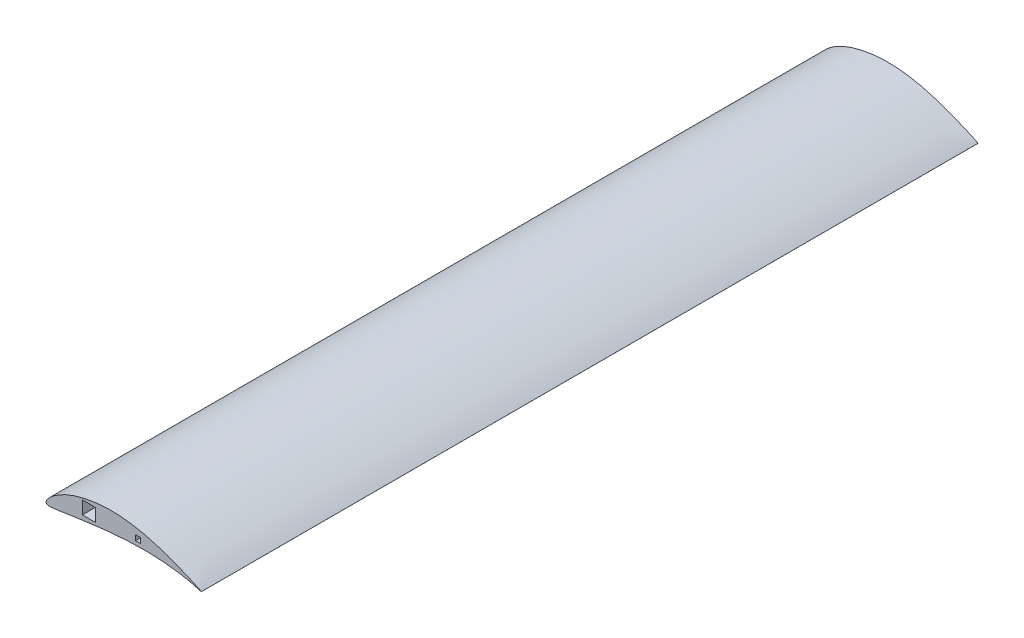
SolidWorks part; units mm, degrees
ref_plane "Front Plane" through (0, 0, 0) normal (0, 0, 1) x (1, 0, 0)
ref_plane "Top Plane" through (0, 0, 0) normal (0, 1, 0) x (1, 0, 0)
ref_plane "Right Plane" through (0, 0, 0) normal (1, 0, 0) x (0, 0, -1)
curve "Curve1"
  spline degree 3 poles (1.0002, -0.0023, 0) (1, 0, 0) (1.0002, 0.0023, 0) (0.9919, 0.0001, 0) (0.9849, 0.0027, 0) (0.9729, 0.003, 0) (0.9609, 0.0043, 0) (0.9483, 0.0054, 0) (0.9357, 0.0065, 0) (0.9231, 0.0077, 0) (0.9104, 0.0088, 0) (0.8978, 0.01, 0) (0.8852, 0.0111, 0) (0.8725, 0.0123, 0) (0.8599, 0.0134, 0) (0.8473, 0.0146, 0) (0.8347, 0.0157, 0) (0.8221, 0.0168, 0) (0.8094, 0.0179, 0) (0.7968, 0.019, 0) (0.7842, 0.0201, 0) (0.7716, 0.0211, 0) (0.759, 0.0222, 0) (0.7464, 0.0232, 0) (0.7337, 0.0243, 0) (0.7211, 0.0253, 0) (0.7085, 0.0263, 0) (0.6959, 0.0273, 0) (0.6833, 0.0283, 0) (0.6706, 0.0293, 0) (0.658, 0.0303, 0) (0.6454, 0.0313, 0) (0.6328, 0.0322, 0) (0.6202, 0.0331, 0) (0.6076, 0.0341, 0) (0.595, 0.035, 0) (0.5823, 0.0358, 0) (0.5697, 0.0367, 0) (0.5571, 0.0375, 0) (0.5446, 0.0384, 0) (0.532, 0.0392, 0) (0.5194, 0.0399, 0) (0.5068, 0.0407, 0) (0.4942, 0.0414, 0) (0.4816, 0.0421, 0) (0.469, 0.0427, 0) (0.4565, 0.0434, 0) (0.4439, 0.044, 0) (0.4313, 0.0445, 0) (0.4188, 0.0451, 0) (0.4062, 0.0456, 0) (0.3936, 0.046, 0) (0.3811, 0.0464, 0) (0.3685, 0.0468, 0) (0.356, 0.0472, 0) (0.3435, 0.0475, 0) (0.3309, 0.0477, 0) (0.3184, 0.0479, 0) (0.3059, 0.0481, 0) (0.2934, 0.0482, 0) (0.2809, 0.0482, 0) (0.2685, 0.0482, 0) (0.256, 0.0481, 0) (0.2436, 0.0479, 0) (0.2312, 0.0477, 0) (0.2189, 0.0474, 0) (0.2065, 0.047, 0) (0.1942, 0.0465, 0) (0.182, 0.0459, 0) (0.1698, 0.0452, 0) (0.1576, 0.0444, 0) (0.1456, 0.0434, 0) (0.1336, 0.0423, 0) (0.1217, 0.0411, 0) (0.1099, 0.0397, 0) (0.0983, 0.038, 0) (0.0868, 0.0362, 0) (0.0756, 0.0342, 0) (0.0647, 0.0319, 0) (0.0541, 0.0294, 0) (0.0441, 0.0266, 0) (0.0348, 0.0236, 0) (0.0266, 0.0205, 0) (0.0197, 0.0175, 0) (0.0142, 0.0146, 0) (0.0101, 0.012, 0) (0.007, 0.0098, 0) (0.0047, 0.0078, 0) (0.003, 0.006, 0) (0.0018, 0.0045, 0) (0.0009, 0.003, 0) (0.0003, 0.0017, 0) (0, 0.0004, 0) (0, -0.0008, 0) (0.0005, -0.0021, 0) (0.0015, -0.0032, 0) (0.0028, -0.0043, 0) (0.0046, -0.0054, 0) (0.0068, -0.0066, 0) (0.0097, -0.0078, 0) (0.0135, -0.0091, 0) (0.0186, -0.0106, 0) (0.0252, -0.0121, 0) (0.0334, -0.0135, 0) (0.043, -0.0148, 0) (0.0536, -0.0159, 0) (0.0648, -0.0167, 0) (0.0764, -0.0173, 0) (0.0882, -0.0177, 0) (0.1003, -0.018, 0) (0.1125, -0.0182, 0) (0.1247, -0.0183, 0) (0.1371, -0.0183, 0) (0.1495, -0.0182, 0) (0.162, -0.0181, 0) (0.1745, -0.0179, 0) (0.187, -0.0176, 0) (0.1996, -0.0174, 0) (0.2122, -0.0171, 0) (0.2248, -0.0167, 0) (0.2375, -0.0164, 0) (0.2501, -0.016, 0) (0.2628, -0.0156, 0) (0.2755, -0.0152, 0) (0.2882, -0.0147, 0) (0.3009, -0.0143, 0) (0.3136, -0.0139, 0) (0.3263, -0.0134, 0) (0.339, -0.0129, 0) (0.3517, -0.0125, 0) (0.3644, -0.012, 0) (0.3771, -0.0116, 0) (0.3897, -0.0111, 0) (0.4024, -0.0106, 0) (0.4151, -0.0102, 0) (0.4277, -0.0098, 0) (0.4404, -0.0093, 0) (0.4531, -0.0089, 0) (0.4657, -0.0085, 0) (0.4784, -0.0081, 0) (0.4911, -0.0077, 0) (0.5037, -0.0073, 0) (0.5164, -0.0069, 0) (0.5291, -0.0066, 0) (0.5417, -0.0062, 0) (0.5544, -0.0059, 0) (0.5671, -0.0055, 0) (0.5798, -0.0052, 0) (0.5924, -0.0049, 0) (0.6051, -0.0046, 0) (0.6178, -0.0044, 0) (0.6304, -0.0041, 0) (0.6431, -0.0039, 0) (0.6558, -0.0036, 0) (0.6685, -0.0034, 0) (0.6811, -0.0032, 0) (0.6938, -0.003, 0) (0.7065, -0.0029, 0) (0.7192, -0.0027, 0) (0.7318, -0.0026, 0) (0.7445, -0.0024, 0) (0.7572, -0.0023, 0) (0.7699, -0.0022, 0) (0.7826, -0.0021, 0) (0.7953, -0.002, 0) (0.8079, -0.0019, 0) (0.8206, -0.0019, 0) (0.8333, -0.0018, 0) (0.846, -0.0017, 0) (0.8588, -0.0017, 0) (0.8715, -0.0016, 0) (0.8842, -0.0015, 0) (0.8969, -0.0015, 0) (0.9096, -0.0014, 0) (0.9223, -0.0013, 0) (0.935, -0.0012, 0) (0.9477, -0.0011, 0) (0.9604, -0.0011, 0) (0.9725, -0.0007, 0) (0.9848, -0.0014, 0) (0.9918, 0.0007, 0) (1.0002, -0.0023, 0) (1, 0, 0) (1.0002, 0.0023, 0) knots -0.007874 -0.002894 -0.000332 0 0.000332 0.002885 0.007815 0.013623 0.01978 0.026037 0.032316 0.038604 0.044895 0.051184 0.057469 0.06375 0.070028 0.076304 0.082578 0.088851 0.095124 0.101396 0.107668 0.113941 0.120213 0.126487 0.132762 0.139036 0.145311 0.151585 0.157859 0.16413 0.170401 0.17667 0.182937 0.189202 0.195466 0.201728 0.207987 0.214245 0.2205 0.226754 0.233005 0.239253 0.2455 0.251744 0.257986 0.264226 0.270464 0.2767 0.282933 0.289165 0.295394 0.30162 0.307843 0.314063 0.32028 0.326491 0.332699 0.3389 0.345096 0.351285 0.357467 0.363641 0.369805 0.375959 0.382101 0.38823 0.394345 0.400443 0.406521 0.412577 0.418607 0.424607 0.430573 0.436498 0.442374 0.448192 0.453938 0.459595 0.465142 0.470542 0.475738 0.480625 0.48504 0.488808 0.491844 0.494208 0.496047 0.497501 0.498679 0.499657 0.500486 0.501199 0.501823 0.502412 0.503041 0.50376 0.504602 0.505602 0.50682 0.508337 0.510284 0.512841 0.516185 0.520365 0.525232 0.530552 0.536146 0.541914 0.547804 0.553781 0.559821 0.565909 0.57203 0.578179 0.584352 0.590546 0.596759 0.60299 0.609237 0.615497 0.621768 0.62805 0.634339 0.640634 0.646932 0.653231 0.659529 0.665824 0.672115 0.678404 0.684692 0.690977 0.69726 0.703542 0.709822 0.716099 0.722375 0.728651 0.734927 0.741206 0.747487 0.753768 0.76005 0.766331 0.772611 0.778892 0.785172 0.791451 0.79773 0.804009 0.810289 0.816569 0.822848 0.829126 0.835406 0.841685 0.847965 0.854245 0.860527 0.866808 0.87309 0.879373 0.885657 0.891942 0.898228 0.904515 0.910804 0.917095 0.923389 0.929686 0.935986 0.942288 0.948588 0.954885 0.961183 0.96748 0.973774 0.980051 0.986247 0.992126 0.997106 0.999668 1 1.000332 1.002885 1.007815 periodic
curve "Curve6"
  spline degree 3 poles (0, 0, 0) (0.0002, 0.0017, 0) (0.0007, 0.0052, 0) (0.0046, 0.01, 0) (0.01, 0.0151, 0) (0.0174, 0.0207, 0) (0.027, 0.0264, 0) (0.0385, 0.0321, 0) (0.052, 0.0379, 0) (0.0675, 0.0434, 0) (0.0847, 0.0488, 0) (0.1038, 0.0538, 0) (0.1245, 0.0586, 0) (0.1469, 0.063, 0) (0.1707, 0.0671, 0) (0.196, 0.0706, 0) (0.2226, 0.0737, 0) (0.2503, 0.0762, 0) (0.2792, 0.0783, 0) (0.3089, 0.0796, 0) (0.3395, 0.0805, 0) (0.3708, 0.0807, 0) (0.4026, 0.0805, 0) (0.4348, 0.0796, 0) (0.4674, 0.0782, 0) (0.5, 0.0763, 0) (0.5327, 0.074, 0) (0.5652, 0.0714, 0) (0.5974, 0.0683, 0) (0.6292, 0.0649, 0) (0.6605, 0.0611, 0) (0.6911, 0.057, 0) (0.7209, 0.0527, 0) (0.7497, 0.0482, 0) (0.7774, 0.0435, 0) (0.804, 0.0388, 0) (0.8292, 0.0342, 0) (0.8531, 0.0298, 0) (0.8754, 0.0255, 0) (0.8961, 0.0215, 0) (0.9151, 0.0177, 0) (0.9324, 0.0142, 0) (0.9478, 0.0111, 0) (0.9613, 0.0083, 0) (0.9728, 0.0059, 0) (0.9823, 0.0039, 0) (0.9897, 0.0023, 0) (0.9949, 0.0006, 0) (0.9983, 0.0007, 0) (0.9996, 0.0001, 0) (1, 0, 0) knots 0 0 0 0 0.004816 0.010311 0.017533 0.026619 0.037456 0.050036 0.064348 0.080358 0.098009 0.117234 0.138018 0.160262 0.183891 0.2088 0.234911 0.262128 0.290345 0.319442 0.34932 0.379858 0.410934 0.442439 0.474224 0.506171 0.538142 0.570006 0.601639 0.632894 0.663653 0.693783 0.723155 0.751647 0.779129 0.805464 0.830536 0.854232 0.876442 0.897072 0.916014 0.933209 0.948567 0.962012 0.9735 0.982962 0.990398 0.99574 0.998893 1 1 1 1
curve "Curve7"
  spline degree 3 poles (0.0009, -0.0041, 0) (-0.0004, 0.0004, 0) (0.0009, 0.0052, 0) (0.0045, 0.01, 0) (0.01, 0.0151, 0) (0.0174, 0.0207, 0) (0.027, 0.0264, 0) (0.0385, 0.0321, 0) (0.052, 0.0379, 0) (0.0675, 0.0434, 0) (0.0847, 0.0488, 0) (0.1038, 0.0538, 0) (0.1245, 0.0586, 0) (0.1469, 0.063, 0) (0.1707, 0.0671, 0) (0.196, 0.0706, 0) (0.2226, 0.0737, 0) (0.2503, 0.0762, 0) (0.2792, 0.0783, 0) (0.3089, 0.0796, 0) (0.3395, 0.0805, 0) (0.3708, 0.0807, 0) (0.4026, 0.0805, 0) (0.4348, 0.0796, 0) (0.4674, 0.0782, 0) (0.5, 0.0763, 0) (0.5327, 0.074, 0) (0.5652, 0.0714, 0) (0.5974, 0.0683, 0) (0.6292, 0.0649, 0) (0.6605, 0.0611, 0) (0.6911, 0.057, 0) (0.7209, 0.0527, 0) (0.7497, 0.0482, 0) (0.7774, 0.0435, 0) (0.804, 0.0388, 0) (0.8292, 0.0342, 0) (0.8531, 0.0298, 0) (0.8754, 0.0255, 0) (0.8961, 0.0215, 0) (0.9151, 0.0177, 0) (0.9324, 0.0142, 0) (0.9478, 0.0111, 0) (0.9613, 0.0083, 0) (0.9728, 0.0059, 0) (0.9823, 0.0038, 0) (0.9896, 0.0024, 0) (0.9953, 0.0005, 0) (0.9978, 0.0008, 0) (1.0006, -0.0001, 0) (0.9977, 0.0003, 0) (0.9953, 0, 0) (0.9896, 0.0009, 0) (0.9823, 0.0014, 0) (0.9728, 0.0025, 0) (0.9613, 0.0036, 0) (0.9478, 0.0048, 0) (0.9324, 0.006, 0) (0.9151, 0.0072, 0) (0.8961, 0.0083, 0) (0.8754, 0.0093, 0) (0.8531, 0.0102, 0) (0.8292, 0.0108, 0) (0.8039, 0.0112, 0) (0.7774, 0.0112, 0) (0.7496, 0.0109, 0) (0.7208, 0.0102, 0) (0.6911, 0.0092, 0) (0.6605, 0.0079, 0) (0.6292, 0.0062, 0) (0.5974, 0.004, 0) (0.5652, 0.0016, 0) (0.5326, -0.0011, 0) (0.5, -0.0039, 0) (0.4673, -0.0069, 0) (0.4348, -0.0098, 0) (0.4026, -0.0128, 0) (0.3708, -0.0154, 0) (0.3395, -0.018, 0) (0.3089, -0.0201, 0) (0.2792, -0.022, 0) (0.2504, -0.0233, 0) (0.2226, -0.0244, 0) (0.1961, -0.0249, 0) (0.1708, -0.0253, 0) (0.147, -0.0252, 0) (0.1246, -0.0248, 0) (0.1039, -0.024, 0) (0.0848, -0.023, 0) (0.0676, -0.0217, 0) (0.0522, -0.0201, 0) (0.0387, -0.0182, 0) (0.0271, -0.0161, 0) (0.0176, -0.0135, 0) (0.01, -0.0109, 0) (0.0046, -0.0077, 0) (0.0009, -0.0041, 0) (-0.0004, 0.0004, 0) (0.0009, 0.0052, 0) knots -0.007287 -0.004212 -0.00188 0 0.002428 0.005198 0.00884 0.013421 0.018885 0.025227 0.032443 0.040515 0.049414 0.059107 0.069586 0.080801 0.092714 0.105273 0.118437 0.13216 0.146386 0.161056 0.17612 0.191517 0.207184 0.223068 0.239094 0.255201 0.27132 0.287385 0.303334 0.319092 0.3346 0.349791 0.364599 0.378965 0.392821 0.406098 0.418739 0.430686 0.441884 0.452285 0.461835 0.470504 0.478247 0.485026 0.490819 0.495589 0.499338 0.502031 0.503621 0.504179 0.504707 0.506286 0.508919 0.512589 0.517281 0.522978 0.529643 0.537254 0.545772 0.555157 0.565377 0.576386 0.588132 0.60057 0.613645 0.627312 0.641507 0.656169 0.671241 0.686661 0.702362 0.718285 0.734352 0.750492 0.766637 0.782713 0.798656 0.81438 0.829825 0.844919 0.8596 0.873808 0.887483 0.900562 0.912999 0.924742 0.935744 0.94596 0.955342 0.963865 0.971494 0.978201 0.983972 0.988807 0.992713 0.995788 0.99812 1 1.002428 1.005198 1.00884 periodic
curve "Curve8"
  spline degree 3 poles (1, 0.0001, 0) (0.9992, 0.0006, 0) (0.9962, 0.0026, 0) (0.9897, 0.0065, 0) (0.9795, 0.0117, 0) (0.966, 0.0177, 0) (0.9494, 0.025, 0) (0.9297, 0.0336, 0) (0.9068, 0.0433, 0) (0.8812, 0.0541, 0) (0.853, 0.0656, 0) (0.8225, 0.0776, 0) (0.79, 0.0897, 0) (0.7558, 0.1017, 0) (0.7202, 0.1132, 0) (0.6835, 0.1241, 0) (0.6459, 0.134, 0) (0.6078, 0.1427, 0) (0.5695, 0.1499, 0) (0.5311, 0.1556, 0) (0.4927, 0.1597, 0) (0.4545, 0.162, 0) (0.4165, 0.1627, 0) (0.3791, 0.1616, 0) (0.3423, 0.1589, 0) (0.3063, 0.1546, 0) (0.2715, 0.1489, 0) (0.2379, 0.1418, 0) (0.2058, 0.1335, 0) (0.1754, 0.124, 0) (0.1469, 0.1134, 0) (0.1204, 0.1018, 0) (0.0962, 0.0895, 0) (0.0744, 0.0767, 0) (0.0552, 0.0638, 0) (0.0386, 0.051, 0) (0.0247, 0.0387, 0) (0.0137, 0.027, 0) (0.0057, 0.0163, 0) (0.0011, 0.0075, 0) (-0.0003, 0.0005, 0) (0.0007, -0.0053, 0) (0.0058, -0.01, 0) (0.0142, -0.0123, 0) (0.0253, -0.0129, 0) (0.0391, -0.0122, 0) (0.0556, -0.0102, 0) (0.0748, -0.0075, 0) (0.0966, -0.0042, 0) (0.1207, -0.0007, 0) (0.1472, 0.0033, 0) (0.1757, 0.0076, 0) (0.206, 0.0121, 0) (0.2381, 0.0168, 0) (0.2716, 0.0215, 0) (0.3064, 0.0261, 0) (0.3423, 0.0305, 0) (0.3791, 0.0347, 0) (0.4165, 0.0385, 0) (0.4544, 0.0419, 0) (0.4926, 0.0448, 0) (0.531, 0.047, 0) (0.5694, 0.0486, 0) (0.6077, 0.0495, 0) (0.6458, 0.0495, 0) (0.6833, 0.0486, 0) (0.7201, 0.0469, 0) (0.7557, 0.0444, 0) (0.7899, 0.0412, 0) (0.8225, 0.0376, 0) (0.853, 0.0334, 0) (0.8812, 0.0289, 0) (0.9069, 0.0241, 0) (0.9297, 0.0193, 0) (0.9494, 0.0145, 0) (0.966, 0.0098, 0) (0.9793, 0.0054, 0) (0.9895, 0.0024, 0) (0.9961, 0.0007, 0) (0.9992, 0.0001, 0) (1, -0.0001, 0) knots 0 0 0 0 0.001413 0.005226 0.010781 0.017816 0.026461 0.036791 0.048686 0.062017 0.076639 0.092363 0.109003 0.126387 0.144339 0.162701 0.181313 0.200023 0.218713 0.237261 0.255692 0.274037 0.292193 0.310133 0.327788 0.345097 0.362002 0.378421 0.394287 0.409543 0.424114 0.437938 0.450942 0.463044 0.474154 0.484165 0.493024 0.500713 0.507126 0.51213 0.514904 0.517171 0.520262 0.524245 0.529498 0.536092 0.544061 0.553363 0.563905 0.575615 0.58842 0.602227 0.616944 0.632457 0.648676 0.665501 0.682818 0.700538 0.718564 0.736789 0.755151 0.773513 0.791878 0.810245 0.828489 0.846493 0.864125 0.881249 0.897725 0.913415 0.928184 0.941897 0.954411 0.965603 0.97535 0.983576 0.990285 0.995433 0.9988 1 1 1 1
sketch "Sketch3" plane through (0, 0, 0) normal (0, 0, 1) x (1, 0, 0)
  line L0 (0, 0) -> (50, 0) construction
  line L1 (0.2298, 0.0405) -> (0.2298, 0.0158) construction
  line L2 (0.1804, 0.0405) -> (0.2298, 0.0405)
  line L3 (0.1804, 0.0405) -> (0.1804, -0.0089)
  line L4 (0.1804, -0.0089) -> (0.2298, -0.0089)
  line L5 (0.2298, 0.0405) -> (0.2298, -0.0089)
  line L6 (0.4642, 0.0242) -> (0.4889, 0.0242)
  line L7 (0.4642, 0.0242) -> (0.4642, -0.0005)
  line L8 (0.4642, -0.0005) -> (0.4889, -0.0005)
  line L9 (0.4889, 0.0242) -> (0.4889, -0.0005)
  line L10 (0.2298, 0.0158) -> (0.2146, 0.0158) construction
  line L11 (0.2146, 0.0158) -> (0.2146, 0.0405) construction
  line L12 (0.2146, 0.0405) -> (0.2298, 0.0405) construction
  line L13 (0, 0) -> (500, 0) construction
  line L14 (0.1804, 0.0458) -> (0.1804, -0.0178) construction
  line L15 (0, 0) -> (0, -165.9812) construction
  line L16 (0, -165.9812) -> (300, -165.9812) construction
  line L17 (72.7802, 36.2202) -> (92.7802, 36.2202) construction
  line L18 (70.2802, 13.7202) -> (95.2802, 13.7202)
  line L19 (70.2802, 13.7202) -> (70.2802, 38.7202)
  line L20 (70.2802, 38.7202) -> (95.2802, 38.7202)
  line L21 (95.2802, 13.7202) -> (95.2802, 38.7202)
  line L22 (92.7802, 16.2202) -> (92.7802, 36.2202) construction
  line L23 (72.7802, 16.2202) -> (92.7802, 16.2202) construction
  line L24 (72.7802, 16.2202) -> (72.7802, 36.2202) construction
  line L25 (300, -0.018) -> (300, 0.015)
  line L26 (172.9506, 31.8748) -> (182.9506, 31.8748)
  line L27 (172.9506, 31.8748) -> (172.9506, 21.8748)
  line L28 (172.9506, 21.8748) -> (182.9506, 21.8748)
  line L29 (182.9506, 31.8748) -> (182.9506, 21.8748)
  spline S0 degree 3 poles (1.0002, -0.0023) (1, 0) (1.0002, 0.0023) (0.9919, 0.0001) (0.9849, 0.0027) (0.9729, 0.003) (0.9609, 0.0043) (0.9483, 0.0054) (0.9357, 0.0065) (0.9231, 0.0077) (0.9104, 0.0088) (0.8978, 0.01) (0.8852, 0.0111) (0.8725, 0.0123) (0.8599, 0.0134) (0.8473, 0.0146) (0.8347, 0.0157) (0.8221, 0.0168) (0.8094, 0.0179) (0.7968, 0.019) (0.7842, 0.0201) (0.7716, 0.0211) (0.759, 0.0222) (0.7464, 0.0232) (0.7337, 0.0243) (0.7211, 0.0253) (0.7085, 0.0263) (0.6959, 0.0273) (0.6833, 0.0283) (0.6706, 0.0293) (0.658, 0.0303) (0.6454, 0.0313) (0.6328, 0.0322) (0.6202, 0.0331) (0.6076, 0.0341) (0.595, 0.035) (0.5823, 0.0358) (0.5697, 0.0367) (0.5571, 0.0375) (0.5446, 0.0384) (0.532, 0.0392) (0.5194, 0.0399) (0.5068, 0.0407) (0.4942, 0.0414) (0.4816, 0.0421) (0.469, 0.0427) (0.4565, 0.0434) (0.4439, 0.044) (0.4313, 0.0445) (0.4188, 0.0451) (0.4062, 0.0456) (0.3936, 0.046) (0.3811, 0.0464) (0.3685, 0.0468) (0.356, 0.0472) (0.3435, 0.0475) (0.3309, 0.0477) (0.3184, 0.0479) (0.3059, 0.0481) (0.2934, 0.0482) (0.2809, 0.0482) (0.2685, 0.0482) (0.256, 0.0481) (0.2436, 0.0479) (0.2312, 0.0477) (0.2189, 0.0474) (0.2065, 0.047) (0.1942, 0.0465) (0.182, 0.0459) (0.1698, 0.0452) (0.1576, 0.0444) (0.1456, 0.0434) (0.1336, 0.0423) (0.1217, 0.0411) (0.1099, 0.0397) (0.0983, 0.038) (0.0868, 0.0362) (0.0756, 0.0342) (0.0647, 0.0319) (0.0541, 0.0294) (0.0441, 0.0266) (0.0348, 0.0236) (0.0266, 0.0205) (0.0197, 0.0175) (0.0142, 0.0146) (0.0101, 0.012) (0.007, 0.0098) (0.0047, 0.0078) (0.003, 0.006) (0.0018, 0.0045) (0.0009, 0.003) (0.0003, 0.0017) (0, 0.0004) (0, -0.0008) (0.0005, -0.0021) (0.0015, -0.0032) (0.0028, -0.0043) (0.0046, -0.0054) (0.0068, -0.0066) (0.0097, -0.0078) (0.0135, -0.0091) (0.0186, -0.0106) (0.0252, -0.0121) (0.0334, -0.0135) (0.043, -0.0148) (0.0536, -0.0159) (0.0648, -0.0167) (0.0764, -0.0173) (0.0882, -0.0177) (0.1003, -0.018) (0.1125, -0.0182) (0.1247, -0.0183) (0.1371, -0.0183) (0.1495, -0.0182) (0.162, -0.0181) (0.1745, -0.0179) (0.187, -0.0176) (0.1996, -0.0174) (0.2122, -0.0171) (0.2248, -0.0167) (0.2375, -0.0164) (0.2501, -0.016) (0.2628, -0.0156) (0.2755, -0.0152) (0.2882, -0.0147) (0.3009, -0.0143) (0.3136, -0.0139) (0.3263, -0.0134) (0.339, -0.0129) (0.3517, -0.0125) (0.3644, -0.012) (0.3771, -0.0116) (0.3897, -0.0111) (0.4024, -0.0106) (0.4151, -0.0102) (0.4277, -0.0098) (0.4404, -0.0093) (0.4531, -0.0089) (0.4657, -0.0085) (0.4784, -0.0081) (0.4911, -0.0077) (0.5037, -0.0073) (0.5164, -0.0069) (0.5291, -0.0066) (0.5417, -0.0062) (0.5544, -0.0059) (0.5671, -0.0055) (0.5798, -0.0052) (0.5924, -0.0049) (0.6051, -0.0046) (0.6178, -0.0044) (0.6304, -0.0041) (0.6431, -0.0039) (0.6558, -0.0036) (0.6685, -0.0034) (0.6811, -0.0032) (0.6938, -0.003) (0.7065, -0.0029) (0.7192, -0.0027) (0.7318, -0.0026) (0.7445, -0.0024) (0.7572, -0.0023) (0.7699, -0.0022) (0.7826, -0.0021) (0.7953, -0.002) (0.8079, -0.0019) (0.8206, -0.0019) (0.8333, -0.0018) (0.846, -0.0017) (0.8588, -0.0017) (0.8715, -0.0016) (0.8842, -0.0015) (0.8969, -0.0015) (0.9096, -0.0014) (0.9223, -0.0013) (0.935, -0.0012) (0.9477, -0.0011) (0.9604, -0.0011) (0.9725, -0.0007) (0.9848, -0.0014) (0.9918, 0.0007) (1.0002, -0.0023) (1, 0) (1.0002, 0.0023) knots -0.007874 -0.002894 -0.000332 0 0.000332 0.002885 0.007815 0.013623 0.01978 0.026037 0.032316 0.038604 0.044895 0.051184 0.057469 0.06375 0.070028 0.076304 0.082578 0.088851 0.095124 0.101396 0.107668 0.113941 0.120213 0.126487 0.132762 0.139036 0.145311 0.151585 0.157859 0.16413 0.170401 0.17667 0.182937 0.189202 0.195466 0.201728 0.207987 0.214245 0.2205 0.226754 0.233005 0.239253 0.2455 0.251744 0.257986 0.264226 0.270464 0.2767 0.282933 0.289165 0.295394 0.30162 0.307843 0.314063 0.32028 0.326491 0.332699 0.3389 0.345096 0.351285 0.357467 0.363641 0.369805 0.375959 0.382101 0.38823 0.394345 0.400443 0.406521 0.412577 0.418607 0.424607 0.430573 0.436498 0.442374 0.448192 0.453938 0.459595 0.465142 0.470542 0.475738 0.480625 0.48504 0.488808 0.491844 0.494208 0.496047 0.497501 0.498679 0.499657 0.500486 0.501199 0.501823 0.502412 0.503041 0.50376 0.504602 0.505602 0.50682 0.508337 0.510284 0.512841 0.516185 0.520365 0.525232 0.530552 0.536146 0.541914 0.547804 0.553781 0.559821 0.565909 0.57203 0.578179 0.584352 0.590546 0.596759 0.60299 0.609237 0.615497 0.621768 0.62805 0.634339 0.640634 0.646932 0.653231 0.659529 0.665824 0.672115 0.678404 0.684692 0.690977 0.69726 0.703542 0.709822 0.716099 0.722375 0.728651 0.734927 0.741206 0.747487 0.753768 0.76005 0.766331 0.772611 0.778892 0.785172 0.791451 0.79773 0.804009 0.810289 0.816569 0.822848 0.829126 0.835406 0.841685 0.847965 0.854245 0.860527 0.866808 0.87309 0.879373 0.885657 0.891942 0.898228 0.904515 0.910804 0.917095 0.923389 0.929686 0.935986 0.942288 0.948588 0.954885 0.961183 0.96748 0.973774 0.980051 0.986247 0.992126 0.997106 0.999668 1 1.000332 1.002885 1.007815 only from (1, 0) to (1, 0) construction
  spline S1 degree 3 poles (1.0002, -0.0023) (1, 0) (1.0002, 0.0023) (0.9919, 0.0001) (0.9849, 0.0027) (0.9729, 0.003) (0.9609, 0.0043) (0.9483, 0.0054) (0.9357, 0.0065) (0.9231, 0.0077) (0.9104, 0.0088) (0.8978, 0.01) (0.8852, 0.0111) (0.8725, 0.0123) (0.8599, 0.0134) (0.8473, 0.0146) (0.8347, 0.0157) (0.8221, 0.0168) (0.8094, 0.0179) (0.7968, 0.019) (0.7842, 0.0201) (0.7716, 0.0211) (0.759, 0.0222) (0.7464, 0.0232) (0.7337, 0.0243) (0.7211, 0.0253) (0.7085, 0.0263) (0.6959, 0.0273) (0.6833, 0.0283) (0.6706, 0.0293) (0.658, 0.0303) (0.6454, 0.0313) (0.6328, 0.0322) (0.6202, 0.0331) (0.6076, 0.0341) (0.595, 0.035) (0.5823, 0.0358) (0.5697, 0.0367) (0.5571, 0.0375) (0.5446, 0.0384) (0.532, 0.0392) (0.5194, 0.0399) (0.5068, 0.0407) (0.4942, 0.0414) (0.4816, 0.0421) (0.469, 0.0427) (0.4565, 0.0434) (0.4439, 0.044) (0.4313, 0.0445) (0.4188, 0.0451) (0.4062, 0.0456) (0.3936, 0.046) (0.3811, 0.0464) (0.3685, 0.0468) (0.356, 0.0472) (0.3435, 0.0475) (0.3309, 0.0477) (0.3184, 0.0479) (0.3059, 0.0481) (0.2934, 0.0482) (0.2809, 0.0482) (0.2685, 0.0482) (0.256, 0.0481) (0.2436, 0.0479) (0.2312, 0.0477) (0.2189, 0.0474) (0.2065, 0.047) (0.1942, 0.0465) (0.182, 0.0459) (0.1698, 0.0452) (0.1576, 0.0444) (0.1456, 0.0434) (0.1336, 0.0423) (0.1217, 0.0411) (0.1099, 0.0397) (0.0983, 0.038) (0.0868, 0.0362) (0.0756, 0.0342) (0.0647, 0.0319) (0.0541, 0.0294) (0.0441, 0.0266) (0.0348, 0.0236) (0.0266, 0.0205) (0.0197, 0.0175) (0.0142, 0.0146) (0.0101, 0.012) (0.007, 0.0098) (0.0047, 0.0078) (0.003, 0.006) (0.0018, 0.0045) (0.0009, 0.003) (0.0003, 0.0017) (0, 0.0004) (0, -0.0008) (0.0005, -0.0021) (0.0015, -0.0032) (0.0028, -0.0043) (0.0046, -0.0054) (0.0068, -0.0066) (0.0097, -0.0078) (0.0135, -0.0091) (0.0186, -0.0106) (0.0252, -0.0121) (0.0334, -0.0135) (0.043, -0.0148) (0.0536, -0.0159) (0.0648, -0.0167) (0.0764, -0.0173) (0.0882, -0.0177) (0.1003, -0.018) (0.1125, -0.0182) (0.1247, -0.0183) (0.1371, -0.0183) (0.1495, -0.0182) (0.162, -0.0181) (0.1745, -0.0179) (0.187, -0.0176) (0.1996, -0.0174) (0.2122, -0.0171) (0.2248, -0.0167) (0.2375, -0.0164) (0.2501, -0.016) (0.2628, -0.0156) (0.2755, -0.0152) (0.2882, -0.0147) (0.3009, -0.0143) (0.3136, -0.0139) (0.3263, -0.0134) (0.339, -0.0129) (0.3517, -0.0125) (0.3644, -0.012) (0.3771, -0.0116) (0.3897, -0.0111) (0.4024, -0.0106) (0.4151, -0.0102) (0.4277, -0.0098) (0.4404, -0.0093) (0.4531, -0.0089) (0.4657, -0.0085) (0.4784, -0.0081) (0.4911, -0.0077) (0.5037, -0.0073) (0.5164, -0.0069) (0.5291, -0.0066) (0.5417, -0.0062) (0.5544, -0.0059) (0.5671, -0.0055) (0.5798, -0.0052) (0.5924, -0.0049) (0.6051, -0.0046) (0.6178, -0.0044) (0.6304, -0.0041) (0.6431, -0.0039) (0.6558, -0.0036) (0.6685, -0.0034) (0.6811, -0.0032) (0.6938, -0.003) (0.7065, -0.0029) (0.7192, -0.0027) (0.7318, -0.0026) (0.7445, -0.0024) (0.7572, -0.0023) (0.7699, -0.0022) (0.7826, -0.0021) (0.7953, -0.002) (0.8079, -0.0019) (0.8206, -0.0019) (0.8333, -0.0018) (0.846, -0.0017) (0.8588, -0.0017) (0.8715, -0.0016) (0.8842, -0.0015) (0.8969, -0.0015) (0.9096, -0.0014) (0.9223, -0.0013) (0.935, -0.0012) (0.9477, -0.0011) (0.9604, -0.0011) (0.9725, -0.0007) (0.9848, -0.0014) (0.9918, 0.0007) (1.0002, -0.0023) (1, 0) (1.0002, 0.0023) knots -0.007874 -0.002894 -0.000332 0 0.000332 0.002885 0.007815 0.013623 0.01978 0.026037 0.032316 0.038604 0.044895 0.051184 0.057469 0.06375 0.070028 0.076304 0.082578 0.088851 0.095124 0.101396 0.107668 0.113941 0.120213 0.126487 0.132762 0.139036 0.145311 0.151585 0.157859 0.16413 0.170401 0.17667 0.182937 0.189202 0.195466 0.201728 0.207987 0.214245 0.2205 0.226754 0.233005 0.239253 0.2455 0.251744 0.257986 0.264226 0.270464 0.2767 0.282933 0.289165 0.295394 0.30162 0.307843 0.314063 0.32028 0.326491 0.332699 0.3389 0.345096 0.351285 0.357467 0.363641 0.369805 0.375959 0.382101 0.38823 0.394345 0.400443 0.406521 0.412577 0.418607 0.424607 0.430573 0.436498 0.442374 0.448192 0.453938 0.459595 0.465142 0.470542 0.475738 0.480625 0.48504 0.488808 0.491844 0.494208 0.496047 0.497501 0.498679 0.499657 0.500486 0.501199 0.501823 0.502412 0.503041 0.50376 0.504602 0.505602 0.50682 0.508337 0.510284 0.512841 0.516185 0.520365 0.525232 0.530552 0.536146 0.541914 0.547804 0.553781 0.559821 0.565909 0.57203 0.578179 0.584352 0.590546 0.596759 0.60299 0.609237 0.615497 0.621768 0.62805 0.634339 0.640634 0.646932 0.653231 0.659529 0.665824 0.672115 0.678404 0.684692 0.690977 0.69726 0.703542 0.709822 0.716099 0.722375 0.728651 0.734927 0.741206 0.747487 0.753768 0.76005 0.766331 0.772611 0.778892 0.785172 0.791451 0.79773 0.804009 0.810289 0.816569 0.822848 0.829126 0.835406 0.841685 0.847965 0.854245 0.860527 0.866808 0.87309 0.879373 0.885657 0.891942 0.898228 0.904515 0.910804 0.917095 0.923389 0.929686 0.935986 0.942288 0.948588 0.954885 0.961183 0.96748 0.973774 0.980051 0.986247 0.992126 0.997106 0.999668 1 1.000332 1.002885 1.007815 only from (1, 0) to (1, 0) construction
  spline S2 degree 3 poles (500.0959, -1.1537) (499.9892, 0.0005) (500.0921, 1.1423) (495.9334, 0.0411) (492.471, 1.3334) (486.441, 1.5239) (480.4457, 2.1624) (474.1516, 2.6955) (467.853, 3.2724) (461.5326, 3.8433) (455.2123, 4.419) (448.8921, 4.9943) (442.5755, 5.5699) (436.262, 6.142) (429.9511, 6.7101) (423.6424, 7.2769) (417.3349, 7.8378) (411.0282, 8.3936) (404.7219, 8.9456) (398.4154, 9.4908) (392.1084, 10.0313) (385.8007, 10.567) (379.4922, 11.0968) (373.1826, 11.6221) (366.8717, 12.1412) (360.56, 12.6562) (354.2482, 13.167) (347.9364, 13.6717) (341.6252, 14.172) (335.3149, 14.6658) (329.0056, 15.1544) (322.6972, 15.6341) (316.3902, 16.1098) (310.0841, 16.5743) (303.7793, 17.0336) (297.4758, 17.4828) (291.1738, 17.9236) (284.8734, 18.3542) (278.5742, 18.7741) (272.2766, 19.1842) (265.9803, 19.5806) (259.6857, 19.9669) (253.3925, 20.3385) (247.1009, 20.6976) (240.8108, 21.0438) (234.5219, 21.3728) (228.2344, 21.6877) (221.9482, 21.986) (215.6634, 22.269) (209.38, 22.5336) (203.0985, 22.7823) (196.8192, 23.011) (190.5422, 23.2214) (184.2678, 23.4112) (177.9968, 23.5814) (171.7294, 23.7279) (165.4666, 23.8538) (159.2085, 23.9536) (152.9563, 24.0285) (146.7104, 24.0763) (140.4718, 24.0951) (134.2418, 24.0833) (128.0212, 24.0398) (121.8114, 23.9589) (115.6139, 23.8431) (109.4305, 23.6857) (103.2636, 23.4864) (97.1155, 23.2386) (90.9895, 22.9417) (84.8889, 22.5902) (78.8182, 22.1795) (72.7826, 21.7035) (66.7884, 21.1583) (60.844, 20.5334) (54.9591, 19.8268) (49.1468, 19.0246) (43.424, 18.1218) (37.8124, 17.1067) (32.343, 15.9694) (27.0604, 14.7062) (22.0393, 13.3164) (17.395, 11.8221) (13.2795, 10.2688) (9.8299, 8.731) (7.0994, 7.2913) (5.0301, 6.0034) (3.4945, 4.8762) (2.3559, 3.8907) (1.5099, 3.0166) (0.8848, 2.2285) (0.4335, 1.5087) (0.1314, 0.8425) (-0.0182, 0.2062) (0.0104, -0.4232) (0.2632, -1.0376) (0.7397, -1.6094) (1.4111, -2.154) (2.2826, -2.7045) (3.4007, -3.2811) (4.8511, -3.898) (6.7651, -4.5654) (9.3055, -5.2886) (12.6143, -6.039) (16.7206, -6.7632) (21.5126, -7.4019) (26.7966, -7.9252) (32.394, -8.3361) (38.1897, -8.6462) (44.118, -8.8675) (50.1404, -9.0195) (56.2306, -9.1096) (62.3698, -9.1496) (68.5456, -9.1443) (74.75, -9.104) (80.9785, -9.0332) (87.2282, -8.9364) (93.4969, -8.818) (99.783, -8.6804) (106.0845, -8.5272) (112.3995, -8.3597) (118.7258, -8.1811) (125.0618, -7.9892) (131.4053, -7.7924) (137.7541, -7.5838) (144.1059, -7.37) (150.4584, -7.1501) (156.8097, -6.9267) (163.1584, -6.6992) (169.5042, -6.4709) (175.8475, -6.2404) (182.1887, -6.0105) (188.5278, -5.7806) (194.865, -5.5531) (201.2002, -5.325) (207.5338, -5.1031) (213.8656, -4.8806) (220.1961, -4.6635) (226.5264, -4.4495) (232.8578, -4.2412) (239.1911, -4.0373) (245.5262, -3.8375) (251.8626, -3.6436) (258.1993, -3.458) (264.5356, -3.2755) (270.8718, -3.1019) (277.2076, -2.9318) (283.5434, -2.7691) (289.8787, -2.6119) (296.2141, -2.4645) (302.5496, -2.3201) (308.8856, -2.184) (315.2216, -2.0569) (321.5574, -1.9335) (327.8933, -1.8191) (334.2294, -1.7131) (340.5661, -1.6125) (346.9033, -1.5208) (353.2413, -1.4364) (359.58, -1.3587) (365.9191, -1.2888) (372.2588, -1.223) (378.5993, -1.1661) (384.9408, -1.1114) (391.2835, -1.0632) (397.6273, -1.0167) (403.9727, -0.9749) (410.3197, -0.9366) (416.669, -0.8947) (423.021, -0.8606) (429.376, -0.8257) (435.7337, -0.7924) (442.0922, -0.7597) (448.4498, -0.726) (454.8061, -0.6894) (461.1609, -0.6473) (467.5175, -0.6036) (473.8564, -0.5446) (480.2008, -0.5303) (486.2618, -0.3697) (492.3763, -0.6848) (495.8827, 0.3278) (500.0959, -1.1537) (499.9892, 0.0005) (500.0921, 1.1423) knots -0.007874 -0.002894 -0.000332 0 0.000332 0.002885 0.007815 0.013623 0.01978 0.026037 0.032316 0.038604 0.044895 0.051184 0.057469 0.06375 0.070028 0.076304 0.082578 0.088851 0.095124 0.101396 0.107668 0.113941 0.120213 0.126487 0.132762 0.139036 0.145311 0.151585 0.157859 0.16413 0.170401 0.17667 0.182937 0.189202 0.195466 0.201728 0.207987 0.214245 0.2205 0.226754 0.233005 0.239253 0.2455 0.251744 0.257986 0.264226 0.270464 0.2767 0.282933 0.289165 0.295394 0.30162 0.307843 0.314063 0.32028 0.326491 0.332699 0.3389 0.345096 0.351285 0.357467 0.363641 0.369805 0.375959 0.382101 0.38823 0.394345 0.400443 0.406521 0.412577 0.418607 0.424607 0.430573 0.436498 0.442374 0.448192 0.453938 0.459595 0.465142 0.470542 0.475738 0.480625 0.48504 0.488808 0.491844 0.494208 0.496047 0.497501 0.498679 0.499657 0.500486 0.501199 0.501823 0.502412 0.503041 0.50376 0.504602 0.505602 0.50682 0.508337 0.510284 0.512841 0.516185 0.520365 0.525232 0.530552 0.536146 0.541914 0.547804 0.553781 0.559821 0.565909 0.57203 0.578179 0.584352 0.590546 0.596759 0.60299 0.609237 0.615497 0.621768 0.62805 0.634339 0.640634 0.646932 0.653231 0.659529 0.665824 0.672115 0.678404 0.684692 0.690977 0.69726 0.703542 0.709822 0.716099 0.722375 0.728651 0.734927 0.741206 0.747487 0.753768 0.76005 0.766331 0.772611 0.778892 0.785172 0.791451 0.79773 0.804009 0.810289 0.816569 0.822848 0.829126 0.835406 0.841685 0.847965 0.854245 0.860527 0.866808 0.87309 0.879373 0.885657 0.891942 0.898228 0.904515 0.910804 0.917095 0.923389 0.929686 0.935986 0.942288 0.948588 0.954885 0.961183 0.96748 0.973774 0.980051 0.986247 0.992126 0.997106 0.999668 1 1.000332 1.002885 1.007815 only from (500, 0) to (500, 0) construction
  spline S3 degree 3 poles (0.0009, 0.0052) (-0.0004, 0.0004) (0.0009, -0.0041) (0.0046, -0.0077) (0.01, -0.0109) (0.0176, -0.0135) (0.0271, -0.0161) (0.0387, -0.0182) (0.0522, -0.0201) (0.0676, -0.0217) (0.0848, -0.023) (0.1039, -0.024) (0.1246, -0.0248) (0.147, -0.0252) (0.1708, -0.0253) (0.1961, -0.0249) (0.2226, -0.0244) (0.2504, -0.0233) (0.2792, -0.022) (0.3089, -0.0201) (0.3395, -0.018) (0.3708, -0.0154) (0.4026, -0.0128) (0.4348, -0.0098) (0.4673, -0.0069) (0.5, -0.0039) (0.5326, -0.0011) (0.5652, 0.0016) (0.5974, 0.004) (0.6292, 0.0062) (0.6605, 0.0079) (0.6911, 0.0092) (0.7208, 0.0102) (0.7496, 0.0109) (0.7774, 0.0112) (0.8039, 0.0112) (0.8292, 0.0108) (0.8531, 0.0102) (0.8754, 0.0093) (0.8961, 0.0083) (0.9151, 0.0072) (0.9324, 0.006) (0.9478, 0.0048) (0.9613, 0.0036) (0.9728, 0.0025) (0.9823, 0.0014) (0.9896, 0.0009) (0.9953, 0) (0.9977, 0.0003) (1.0006, -0.0001) (0.9978, 0.0008) (0.9953, 0.0005) (0.9896, 0.0024) (0.9823, 0.0038) (0.9728, 0.0059) (0.9613, 0.0083) (0.9478, 0.0111) (0.9324, 0.0142) (0.9151, 0.0177) (0.8961, 0.0215) (0.8754, 0.0255) (0.8531, 0.0298) (0.8292, 0.0342) (0.804, 0.0388) (0.7774, 0.0435) (0.7497, 0.0482) (0.7209, 0.0527) (0.6911, 0.057) (0.6605, 0.0611) (0.6292, 0.0649) (0.5974, 0.0683) (0.5652, 0.0714) (0.5327, 0.074) (0.5, 0.0763) (0.4674, 0.0782) (0.4348, 0.0796) (0.4026, 0.0805) (0.3708, 0.0807) (0.3395, 0.0805) (0.3089, 0.0796) (0.2792, 0.0783) (0.2503, 0.0762) (0.2226, 0.0737) (0.196, 0.0706) (0.1707, 0.0671) (0.1469, 0.063) (0.1245, 0.0586) (0.1038, 0.0538) (0.0847, 0.0488) (0.0675, 0.0434) (0.052, 0.0379) (0.0385, 0.0321) (0.027, 0.0264) (0.0174, 0.0207) (0.01, 0.0151) (0.0045, 0.01) (0.0009, 0.0052) (-0.0004, 0.0004) (0.0009, -0.0041) knots -0.00884 -0.005198 -0.002428 0 0.00188 0.004212 0.007287 0.011193 0.016028 0.021799 0.028506 0.036135 0.044658 0.05404 0.064256 0.075258 0.087001 0.099438 0.112517 0.126192 0.1404 0.155081 0.170175 0.18562 0.201344 0.217287 0.233363 0.249508 0.265648 0.281715 0.297638 0.313339 0.328759 0.343831 0.358493 0.372688 0.386355 0.39943 0.411868 0.423614 0.434623 0.444843 0.454228 0.462746 0.470357 0.477022 0.482719 0.487411 0.491081 0.493714 0.495293 0.495821 0.496379 0.497969 0.500662 0.504411 0.509181 0.514974 0.521753 0.529496 0.538165 0.547715 0.558116 0.569314 0.581261 0.593902 0.607179 0.621035 0.635401 0.650209 0.6654 0.680908 0.696666 0.712615 0.72868 0.744799 0.760906 0.776932 0.792816 0.808483 0.82388 0.838944 0.853614 0.86784 0.881563 0.894727 0.907286 0.919199 0.930414 0.940893 0.950586 0.959485 0.967557 0.974773 0.981115 0.986579 0.99116 0.994802 0.997572 1 1.00188 1.004212 1.007287 only from (0, 0) to (0, 0) construction
  spline S4 degree 3 poles (0.0009, 0.0052) (-0.0004, 0.0004) (0.0009, -0.0041) (0.0046, -0.0077) (0.01, -0.0109) (0.0176, -0.0135) (0.0271, -0.0161) (0.0387, -0.0182) (0.0522, -0.0201) (0.0676, -0.0217) (0.0848, -0.023) (0.1039, -0.024) (0.1246, -0.0248) (0.147, -0.0252) (0.1708, -0.0253) (0.1961, -0.0249) (0.2226, -0.0244) (0.2504, -0.0233) (0.2792, -0.022) (0.3089, -0.0201) (0.3395, -0.018) (0.3708, -0.0154) (0.4026, -0.0128) (0.4348, -0.0098) (0.4673, -0.0069) (0.5, -0.0039) (0.5326, -0.0011) (0.5652, 0.0016) (0.5974, 0.004) (0.6292, 0.0062) (0.6605, 0.0079) (0.6911, 0.0092) (0.7208, 0.0102) (0.7496, 0.0109) (0.7774, 0.0112) (0.8039, 0.0112) (0.8292, 0.0108) (0.8531, 0.0102) (0.8754, 0.0093) (0.8961, 0.0083) (0.9151, 0.0072) (0.9324, 0.006) (0.9478, 0.0048) (0.9613, 0.0036) (0.9728, 0.0025) (0.9823, 0.0014) (0.9896, 0.0009) (0.9953, 0) (0.9977, 0.0003) (1.0006, -0.0001) (0.9978, 0.0008) (0.9953, 0.0005) (0.9896, 0.0024) (0.9823, 0.0038) (0.9728, 0.0059) (0.9613, 0.0083) (0.9478, 0.0111) (0.9324, 0.0142) (0.9151, 0.0177) (0.8961, 0.0215) (0.8754, 0.0255) (0.8531, 0.0298) (0.8292, 0.0342) (0.804, 0.0388) (0.7774, 0.0435) (0.7497, 0.0482) (0.7209, 0.0527) (0.6911, 0.057) (0.6605, 0.0611) (0.6292, 0.0649) (0.5974, 0.0683) (0.5652, 0.0714) (0.5327, 0.074) (0.5, 0.0763) (0.4674, 0.0782) (0.4348, 0.0796) (0.4026, 0.0805) (0.3708, 0.0807) (0.3395, 0.0805) (0.3089, 0.0796) (0.2792, 0.0783) (0.2503, 0.0762) (0.2226, 0.0737) (0.196, 0.0706) (0.1707, 0.0671) (0.1469, 0.063) (0.1245, 0.0586) (0.1038, 0.0538) (0.0847, 0.0488) (0.0675, 0.0434) (0.052, 0.0379) (0.0385, 0.0321) (0.027, 0.0264) (0.0174, 0.0207) (0.01, 0.0151) (0.0045, 0.01) (0.0009, 0.0052) (-0.0004, 0.0004) (0.0009, -0.0041) knots -0.00884 -0.005198 -0.002428 0 0.00188 0.004212 0.007287 0.011193 0.016028 0.021799 0.028506 0.036135 0.044658 0.05404 0.064256 0.075258 0.087001 0.099438 0.112517 0.126192 0.1404 0.155081 0.170175 0.18562 0.201344 0.217287 0.233363 0.249508 0.265648 0.281715 0.297638 0.313339 0.328759 0.343831 0.358493 0.372688 0.386355 0.39943 0.411868 0.423614 0.434623 0.444843 0.454228 0.462746 0.470357 0.477022 0.482719 0.487411 0.491081 0.493714 0.495293 0.495821 0.496379 0.497969 0.500662 0.504411 0.509181 0.514974 0.521753 0.529496 0.538165 0.547715 0.558116 0.569314 0.581261 0.593902 0.607179 0.621035 0.635401 0.650209 0.6654 0.680908 0.696666 0.712615 0.72868 0.744799 0.760906 0.776932 0.792816 0.808483 0.82388 0.838944 0.853614 0.86784 0.881563 0.894727 0.907286 0.919199 0.930414 0.940893 0.950586 0.959485 0.967557 0.974773 0.981115 0.986579 0.99116 0.994802 0.997572 1 1.00188 1.004212 1.007287 only from (0, 0) to (0, 0)
  spline S6 degree 3 poles (1643.0294, 2510.6121) (-0.9132, -4.9999) (1.4845, -0.2863) (0.9897, 0.0065) (0.9795, 0.0117) (0.966, 0.0177) (0.9494, 0.025) (0.9297, 0.0336) (0.8975, 0.0473) (0.8617, 0.0622) (0.8225, 0.0776) (0.79, 0.0897) (0.7558, 0.1017) (0.7079, 0.1172) (0.6584, 0.1311) (0.6078, 0.1427) (0.5695, 0.1499) (0.5311, 0.1556) (0.4927, 0.1597) (0.4545, 0.162) (0.4165, 0.1627) (0.3791, 0.1616) (0.3305, 0.1581) (0.2833, 0.1514) (0.2379, 0.1418) (0.2058, 0.1335) (0.1754, 0.124) (0.1469, 0.1134) (0.1204, 0.1018) (0.0962, 0.0895) (0.0744, 0.0767) (0.0552, 0.0638) (0.0386, 0.051) (0.0247, 0.0387) (0.0137, 0.027) (0.0057, 0.0163) (0.0011, 0.0075) (-0.0003, 0.0005) (0.0007, -0.0053) (0.0058, -0.01) (0.0142, -0.0123) (0.0253, -0.0129) (0.0391, -0.0122) (0.0556, -0.0102) (0.0748, -0.0075) (0.0966, -0.0042) (0.1207, -0.0007) (0.1472, 0.0033) (0.1757, 0.0076) (0.2172, 0.0138) (0.2609, 0.02) (0.3311, 0.0293) (0.3922, 0.0363) (0.4672, 0.043) (0.531, 0.0474) (0.5949, 0.0495) (0.6458, 0.0495) (0.6833, 0.0486) (0.7201, 0.0469) (0.7557, 0.0444) (0.7899, 0.0412) (0.8225, 0.0376) (0.853, 0.0334) (0.8812, 0.0289) (0.9069, 0.0241) (0.9297, 0.0193) (0.9494, 0.0145) (0.966, 0.0098) (0.9793, 0.0054) (0.9895, 0.0024) (1.5167, -0.1309) (3.0282, 4.3648) (-623.5231, -2934.0731) knots -0.813001 -0.813001 -0.813001 -0.813001 0.001413 0.005226 0.010781 0.017816 0.026461 0.036791 0.048686 0.076639 0.092363 0.109003 0.126387 0.144339 0.181313 0.200023 0.218713 0.237261 0.255692 0.274037 0.292193 0.310133 0.327788 0.362002 0.378421 0.394287 0.409543 0.424114 0.437938 0.450942 0.463044 0.474154 0.484165 0.493024 0.500713 0.507126 0.51213 0.514904 0.517171 0.520262 0.524245 0.529498 0.536092 0.544061 0.553363 0.563905 0.575615 0.58842 0.602227 0.616944 0.648676 0.665501 0.718564 0.736789 0.773513 0.810245 0.828489 0.846493 0.864125 0.881249 0.897725 0.913415 0.928184 0.941897 0.954411 0.965603 0.97535 0.983576 0.990285 0.995433 0.9988 1.769799 1.769799 1.769799 1.769799 only from (1, 0.0001) to (1, -0.0001) construction
  spline S7 degree 3 poles (1, 0.0001) (0.9992, 0.0006) (0.9962, 0.0026) (0.9897, 0.0065) (0.9795, 0.0117) (0.966, 0.0177) (0.9494, 0.025) (0.9297, 0.0336) (0.8975, 0.0473) (0.8617, 0.0622) (0.8225, 0.0776) (0.79, 0.0897) (0.7558, 0.1017) (0.7079, 0.1172) (0.6584, 0.1311) (0.6078, 0.1427) (0.5695, 0.1499) (0.5311, 0.1556) (0.4927, 0.1597) (0.4545, 0.162) (0.4165, 0.1627) (0.3791, 0.1616) (0.3305, 0.1581) (0.2833, 0.1514) (0.2379, 0.1418) (0.2058, 0.1335) (0.1754, 0.124) (0.1469, 0.1134) (0.1204, 0.1018) (0.0962, 0.0895) (0.0744, 0.0767) (0.0552, 0.0638) (0.0386, 0.051) (0.0247, 0.0387) (0.0137, 0.027) (0.0057, 0.0163) (0.0011, 0.0075) (-0.0003, 0.0005) (0.0007, -0.0053) (0.0058, -0.01) (0.0142, -0.0123) (0.0253, -0.0129) (0.0391, -0.0122) (0.0556, -0.0102) (0.0748, -0.0075) (0.0966, -0.0042) (0.1207, -0.0007) (0.1472, 0.0033) (0.1757, 0.0076) (0.2172, 0.0138) (0.2609, 0.02) (0.3311, 0.0293) (0.3922, 0.0363) (0.4672, 0.043) (0.531, 0.0474) (0.5949, 0.0495) (0.6458, 0.0495) (0.6833, 0.0486) (0.7201, 0.0469) (0.7557, 0.0444) (0.7899, 0.0412) (0.8225, 0.0376) (0.853, 0.0334) (0.8812, 0.0289) (0.9069, 0.0241) (0.9297, 0.0193) (0.9494, 0.0145) (0.966, 0.0098) (0.9793, 0.0054) (0.9895, 0.0024) (0.9961, 0.0007) (0.9992, 0.0001) (1, -0.0001) knots 0 0 0 0 0.001413 0.005226 0.010781 0.017816 0.026461 0.036791 0.048686 0.076639 0.092363 0.109003 0.126387 0.144339 0.181313 0.200023 0.218713 0.237261 0.255692 0.274037 0.292193 0.310133 0.327788 0.362002 0.378421 0.394287 0.409543 0.424114 0.437938 0.450942 0.463044 0.474154 0.484165 0.493024 0.500713 0.507126 0.51213 0.514904 0.517171 0.520262 0.524245 0.529498 0.536092 0.544061 0.553363 0.563905 0.575615 0.58842 0.602227 0.616944 0.648676 0.665501 0.718564 0.736789 0.773513 0.810245 0.828489 0.846493 0.864125 0.881249 0.897725 0.913415 0.928184 0.941897 0.954411 0.965603 0.97535 0.983576 0.990285 0.995433 0.9988 1 1 1 1
  spline S8 degree 3 poles (300, 0.015) (299.7549, 0.1803) (298.8485, 0.7916) (296.9058, 1.9408) (293.8466, 3.4981) (289.7862, 5.3006) (284.8109, 7.501) (278.8968, 10.0932) (269.2354, 14.1942) (258.4984, 18.6488) (246.7587, 23.2716) (237.0102, 26.9128) (226.7497, 30.5099) (212.3568, 35.1631) (197.5225, 39.3346) (182.3532, 42.7985) (170.8532, 44.983) (159.3316, 46.6908) (147.8202, 47.91) (136.3478, 48.6095) (124.9585, 48.8071) (113.7162, 48.4849) (99.1486, 47.4166) (84.9892, 45.4203) (71.3746, 42.5477) (61.7481, 40.04) (52.6211, 37.1899) (44.0583, 34.0079) (36.1164, 30.545) (28.8549, 26.8491) (22.3219, 23.0051) (16.5503, 19.1272) (11.572, 15.306) (7.4224, 11.6043) (4.1227, 8.1029) (1.7178, 4.9011) (0.3395, 2.2392) (-0.1024, 0.1583) (0.204, -1.5858) (1.7337, -3.0118) (4.2692, -3.6752) (7.5793, -3.8829) (11.7249, -3.6469) (16.6836, -3.0728) (22.4426, -2.246) (28.9693, -1.2656) (36.224, -0.1978) (44.1511, 0.9911) (52.7004, 2.2732) (65.1658, 4.1342) (78.2672, 6.0122) (99.3394, 8.8005) (117.6535, 10.8907) (140.1569, 12.9054) (159.2914, 14.2176) (178.4661, 14.8407) (193.7325, 14.8395) (205.0007, 14.5833) (216.0252, 14.0626) (226.7164, 13.3188) (236.9837, 12.3748) (246.7404, 11.2771) (255.8965, 10.033) (264.365, 8.6788) (272.0599, 7.2435) (278.9039, 5.7843) (284.8344, 4.3498) (289.7985, 2.9258) (293.7954, 1.6329) (296.8452, 0.7155) (298.8166, 0.2169) (299.7538, 0.0309) (300, -0.018) knots 0 0 0 0 0.001413 0.005226 0.010781 0.017816 0.026461 0.036791 0.048686 0.076639 0.092363 0.109003 0.126387 0.144339 0.181313 0.200023 0.218713 0.237261 0.255692 0.274037 0.292193 0.310133 0.327788 0.362002 0.378421 0.394287 0.409543 0.424114 0.437938 0.450942 0.463044 0.474154 0.484165 0.493024 0.500713 0.507126 0.51213 0.514904 0.517171 0.520262 0.524245 0.529498 0.536092 0.544061 0.553363 0.563905 0.575615 0.58842 0.602227 0.616944 0.648676 0.665501 0.718564 0.736789 0.773513 0.810245 0.828489 0.846493 0.864125 0.881249 0.897725 0.913415 0.928184 0.941897 0.954411 0.965603 0.97535 0.983576 0.990285 0.995433 0.9988 1 1 1 1
  dimension "D1" = 300
  dimension "D2" = 25
  dimension "D3" = 2.5
  dimension "D4" = 20
  dimension "D5" = 10
extrude "Boss-Extrude1" add sketch "Sketch3" along normal blind 1500 contours L25 S8 L3 L2 L5 L4 L26 L29 L28 L27 L6 L9 L8 L7 L21 L18 L19 L20 region at (0.2962, 0.0449, 0) region at (0.1705, -0.0003, 0) region at (0.005, -0.0079, 0) region at (125.7868, 23.7644, 0) region at (0.8963, 0.0231, 0) region at (0.4716, 0.099, 0) region at (0.9981, 0.0004, 0)
ref_plane "Plane1" through (100, 0, 0) normal (1, 0, 0) x (0, 0, -1)
